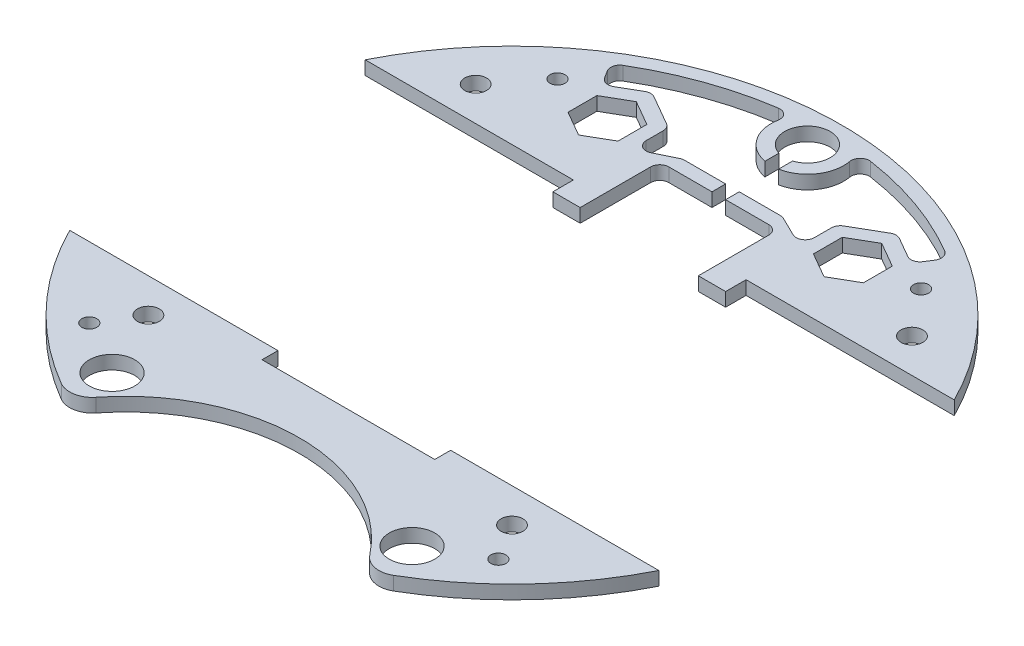
SolidWorks part; units mm, degrees
material "Acrylic (Medium-high impact)"
ref_plane "Front Plane" through (0, 0, 0) normal (0, 0, 1) x (1, 0, 0)
ref_plane "Top Plane" through (0, 0, 0) normal (0, 1, 0) x (1, 0, 0)
ref_plane "Right Plane" through (0, 0, 0) normal (1, 0, 0) x (0, 0, -1)
sketch "Sketch1" plane through (0, 0, 0) normal (0, 1, 0) x (1, 0, 0)
  line L0 (0, -85) -> (-32.4891, -64.8129) construction
  line L1 (0, -85) -> (0, 0) construction
  arc A0 (36.5434, -62.6165) -> (-36.5434, -62.6165) centre (0, 0) ccw
  arc A1 (30.0898, -61.3851) -> (-30.0898, -61.3851) centre (0, -85) ccw
  arc A2 (36.5434, -62.6165) -> (30.0898, -61.3851) centre (34.0231, -58.2982) cw
  arc A3 (-30.0898, -61.3851) -> (-36.5434, -62.6165) centre (-34.0231, -58.2982) cw
  dimension "D1" = 145
  dimension "D2" = 76.5
  dimension "D4" = 5
  dimension "D3" = 85
extrude "Boss-Extrude1" add sketch "Sketch1" along normal blind 3
sketch "solenoid placement" plane through (0, 3, 0) normal (0, 1, 0) x (1, 0, 0)
  line L4 (-19, -36) -> (19, -36)
  line L5 (-19, 28) -> (-19, -36)
  line L6 (19, 28) -> (-19, 28)
  line L7 (19, -36) -> (19, 28)
  line L8 (-19, -36) -> (19, -36)
  line L9 (-19, 28) -> (-19, -36)
  line L10 (19, 28) -> (-19, 28)
  line L11 (19, -36) -> (19, 28)
  dimension "D1" = 0
extrude "Cut-Extrude1" cut sketch "solenoid placement" against normal through all
sketch "Sketch5" plane through (0, 3, 0) normal (0, 1, 0) x (1, 0, 0)
  line L12 (-21.5, 51.1754) -> (-27, 54.3509)
  line L13 (-27, 54.3509) -> (-32.5, 51.1754)
  line L14 (-32.5, 51.1754) -> (-32.5, 44.8246)
  line L15 (-32.5, 44.8246) -> (-27, 41.6491)
  line L16 (-27, 41.6491) -> (-21.5, 44.8246)
  line L17 (-21.5, 44.8246) -> (-21.5, 51.1754)
  line L18 (-21.5, 51.1754) -> (-27, 54.3509)
  line L19 (-27, 54.3509) -> (-32.5, 51.1754)
  line L20 (-32.5, 51.1754) -> (-32.5, 44.8246)
  line L21 (-32.5, 44.8246) -> (-27, 41.6491)
  line L22 (-27, 41.6491) -> (-21.5, 44.8246)
  line L23 (-21.5, 44.8246) -> (-21.5, 51.1754)
  line L24 (21.5, 51.1754) -> (21.5, 44.8246)
  line L25 (21.5, 44.8246) -> (27, 41.6491)
  line L26 (27, 41.6491) -> (32.5, 44.8246)
  line L27 (32.5, 44.8246) -> (32.5, 51.1754)
  line L28 (32.5, 51.1754) -> (27, 54.3509)
  line L29 (27, 54.3509) -> (21.5, 51.1754)
  line L42 (21.5, 51.1754) -> (21.5, 44.8246)
  line L43 (21.5, 44.8246) -> (27, 41.6491)
  line L44 (27, 41.6491) -> (32.5, 44.8246)
  line L45 (32.5, 44.8246) -> (32.5, 51.1754)
  line L46 (32.5, 51.1754) -> (27, 54.3509)
  line L47 (27, 54.3509) -> (21.5, 51.1754)
  dimension "D1" = 0
  dimension "D2" = 0
extrude "Cut-Extrude5" cut sketch "Sketch5" against normal through all
sketch "Sketch6" plane through (0, 3, 0) normal (0, 1, 0) x (1, 0, 0)
  circle A0 centre (48, 40) radius 2.4
  circle A1 centre (40, -40) radius 2.4
  circle A2 centre (40, -40) radius 2.4 construction
  circle A3 centre (-40, -40) radius 2.4
  circle A4 centre (-40, -40) radius 2.4 construction
  circle A5 centre (48, 40) radius 2.4
  circle A6 centre (48, 40) radius 2.4 construction
  circle A7 centre (-48, 40) radius 2.4
  circle A8 centre (-48, 40) radius 2.4 construction
  circle A9 centre (-48, 40) radius 2.4
  circle A10 centre (40, -40) radius 2.4
  circle A11 centre (-40, -40) radius 2.4
  dimension "D5" = 4.8
extrude "Cut-Extrude6" cut sketch "Sketch6" against normal through all
sketch "Sketch3" plane through (0, 3, 0) normal (0, 1, 0) x (1, 0, 0)
  line L0 (-19, 28) -> (-19, 32.5)
  line L1 (72.5, -32.5) -> (-72.5, -32.5)
  line L2 (72.5, -32.5) -> (72.5, 32.5)
  line L3 (72.5, 32.5) -> (19, 32.5)
  line L4 (-72.5, -32.5) -> (-72.5, 32.5)
  line L5 (72.5, -32.5) -> (-72.5, 32.5) construction
  line L6 (72.5, 32.5) -> (-72.5, -32.5) construction
  line L7 (-19, 28) -> (19, 28)
  line L8 (19, 28) -> (19, 32.5)
  line L9 (-19, 32.5) -> (-72.5, 32.5)
  line L10 (-19, 28) -> (-19, -36) construction
  arc A0 (36.5434, -62.6165) -> (-36.5434, -62.6165) centre (0, 0) ccw construction
  point P0 (0, 0)
  dimension "D1" = 65
extrude "Cut-Extrude3" cut sketch "Sketch3" against normal through all
sketch "Sketch7" plane through (0, 3, 0) normal (0, 1, 0) x (1, 0, 0)
  line L8 (13, 28) -> (13, 43.5)
  line L9 (-13, 28) -> (13, 28)
  line L10 (-13, 43.5) -> (-13, 28)
  line L11 (11, 45.5) -> (-11, 45.5)
  line L28 (13, 28) -> (13, 43.5)
  line L29 (-13, 28) -> (13, 28)
  line L30 (-13, 43.5) -> (-13, 28)
  line L31 (11, 45.5) -> (-11, 45.5)
  arc A4 (-11, 45.5) -> (-13, 43.5) centre (-11, 43.5) ccw
  arc A5 (13, 43.5) -> (11, 45.5) centre (11, 43.5) ccw
  arc A14 (-11, 45.5) -> (-13, 43.5) centre (-11, 43.5) ccw
  arc A15 (13, 43.5) -> (11, 45.5) centre (11, 43.5) ccw
  dimension "D1" = 0
extrude "Cut-Extrude7" cut sketch "Sketch7" against normal through all
sketch "Sketch8" plane through (0, 3, 0) normal (0, 1, 0) x (1, 0, 0)
  line L0 (0, 0) -> (0, -21.9152) construction
  circle A1 centre (33, -55) radius 5
  circle A4 centre (-33, -55) radius 5
  dimension "D3" = 10
  dimension "D1" = 33
  dimension "D2" = 55
extrude "Cut-Extrude8" cut sketch "Sketch8" against normal through all
sketch "Sketch9" plane through (0, 3, 0) normal (0, 1, 0) x (1, 0, 0)
  line L0 (0, 0) -> (0, 65) construction
  line L1 (1.5, 0) -> (1.5, 60.2303)
  line L2 (-1.5, 0) -> (-1.5, 60.2303)
  line L3 (1.5, 0) -> (1.5, 65) construction
  line L4 (-1.5, 0) -> (-1.5, 65) construction
  arc A0 (1.5, 60.2303) -> (-1.5, 60.2303) centre (0, 65) ccw
  arc A1 (1.5, 0) -> (-1.5, 0) centre (0, 0) cw
  dimension "D1" = 10
  dimension "D2" = 65
  dimension "D3" = 1.5
  dimension "D4" = 1.5
extrude "Cut-Extrude9" cut sketch "Sketch9" against normal through all
sketch "Sketch10" plane through (0, 3, 0) normal (0, 1, 0) x (1, 0, 0)
  line L0 (0, 0) -> (0, -25.927) construction
  circle A0 centre (45, -48) radius 1.65
  circle A1 centre (-45, -48) radius 1.65
  circle A2 centre (40, 50) radius 1.65
  circle A3 centre (-40, 50) radius 1.65
  dimension "D3" = 3.3
  dimension "D1" = 45
  dimension "D2" = 48
  dimension "D4" = 40
  dimension "D5" = 50
extrude "Cut-Extrude10" cut sketch "Sketch10" against normal blind 10
sketch "Sketch11" plane through (0, 3, 0) normal (0, 1, 0) x (1, 0, 0)
  line L0 (-1.5, 48.5) -> (1.5, 48.5)
  line L1 (-15.6199, 46.236) -> (-11.4164, 48.2959)
  line L2 (11.4164, 48.2959) -> (15.6199, 46.236)
  line L3 (35.0267, 55.3973) -> (36.0573, 57.0273)
  line L4 (-35.0267, 55.3973) -> (-36.0573, 57.0273)
  line L11 (-18.5, 44.8246) -> (-18.5, 52.9075)
  line L12 (-18.5, 52.9075) -> (-27, 57.815)
  line L13 (-27, 57.815) -> (-34, 53.7735)
  line L14 (-18.5, 48.0319) -> (-18.5, 51.7528)
  line L15 (-19.5, 53.4848) -> (-26, 57.2376)
  line L16 (-28, 57.2376) -> (-32.3362, 54.7341)
  line L19 (-1.5, 48.5) -> (-11, 48.5)
  line L20 (-1.5, 48.5) -> (-10.5363, 48.5)
  line L22 (11, 48.5) -> (1.5, 48.5)
  line L23 (10.5363, 48.5) -> (1.5, 48.5)
  line L32 (34, 53.7735) -> (27, 57.815)
  line L33 (27, 57.815) -> (18.5, 52.9075)
  line L34 (18.5, 52.9075) -> (18.5, 44.8246)
  line L35 (32.3362, 54.7341) -> (28, 57.2376)
  line L36 (26, 57.2376) -> (19.5, 53.4848)
  line L37 (18.5, 51.7528) -> (18.5, 48.0319)
  arc A0 (-7.8724, 66.4231) -> (-10.1321, 68.7575) centre (-9.8405, 66.7788) ccw
  arc A1 (7.8724, 66.4231) -> (10.1321, 68.7575) centre (9.8405, 66.7788) cw
  arc A2 (2.4, 57.3685) -> (-2.4, 57.3685) centre (0, 65) ccw
  arc A3 (0, 57) -> (7.8724, 66.4231) centre (0, 65) ccw
  arc A4 (-7.8724, 66.4231) -> (0, 57) centre (0, 65) ccw
  arc A5 (62.1257, 31.1552) -> (-62.1257, 31.1552) centre (0, 0) ccw
  arc A6 (35.3852, 59.8175) -> (10.1321, 68.7575) centre (0, 0) ccw
  arc A7 (-10.1321, 68.7575) -> (-35.3852, 59.8175) centre (0, 0) ccw
  arc A8 (36.0573, 57.0273) -> (35.3852, 59.8175) centre (34.3669, 58.0962) ccw
  arc A9 (32.3362, 54.7341) -> (35.0267, 55.3973) centre (33.3362, 56.4661) ccw
  arc A10 (28, 57.2376) -> (26, 57.2376) centre (27, 55.5056) ccw
  arc A11 (19.5, 53.4848) -> (18.5, 51.7528) centre (20.5, 51.7528) ccw
  arc A12 (18.5, 48.0319) -> (15.6199, 46.236) centre (16.5, 48.0319) cw
  arc A13 (10.5363, 48.5) -> (11.4164, 48.2959) centre (10.5363, 46.5) cw
  arc A14 (-10.5363, 48.5) -> (-11.4164, 48.2959) centre (-10.5363, 46.5) ccw
  arc A15 (-18.5, 48.0319) -> (-15.6199, 46.236) centre (-16.5, 48.0319) ccw
  arc A16 (-18.5, 51.7528) -> (-19.5, 53.4848) centre (-20.5, 51.7528) ccw
  arc A17 (-26, 57.2376) -> (-28, 57.2376) centre (-27, 55.5056) ccw
  arc A18 (-32.3362, 54.7341) -> (-35.0267, 55.3973) centre (-33.3362, 56.4661) cw
  arc A19 (-36.0573, 57.0273) -> (-35.3852, 59.8175) centre (-34.3669, 58.0962) cw
  point P27 (-6.8312, 69.1635)
  dimension "D7" = 2
  dimension "D1" = 3
  dimension "D2" = 3
  dimension "D3" = 3
  dimension "D4" = 3
  dimension "D5" = 3
  dimension "D6" = 3
extrude "Cut-Extrude11" cut sketch "Sketch11" against normal through all
equation "\"smallPulleyTeeth\"= 30"
equation "\"largePulleyTeeth\"= 30"
equation "\"eighthThick\"= 3.0mm"
equation "\"sixteenthThick\"= 1.7mm"
equation "\"quarterThick\"=6.0mm"
equation "\"OD\"= 145mm"
equation "\"puckAngle\"= 60.5deg"
equation "\"D1@Sketch1\"=\"OD\""
equation "\"puckDiam\"= 76.5mm"
equation "\"D2@Sketch1\"=\"puckDiam\""
equation "\"D1@Boss-Extrude1\"=\"eighthThick\""
equation "\"axlePress\"= 5.9mm"
equation "\"press\"= 0.2mm"
equation "\"wheelClear\"= 0.3mm"
equation "\"10-32clear\"= 4.8mm"
equation "\"6-32clear\"= 3.3mm"
equation "\"8-32clear\"= 4.0mm"
equation "\"wheelHeight\"= 22mm"
equation "\"wheelWell\"= 65mm"
equation "\"D1@Sketch3\"=\"wheelWell\""
equation "\"puckDist\"= 85mm"
equation "\"scoopFillet\"= 5mm"
equation "\"4-40clear\"= 3.0mm"
equation "\"D3@Sketch1\"=\"puckDist\""
equation "\"D4@Sketch1\"=\"scoopFillet\""
equation "\"10-32tap\"= 4.45mm"
equation "\"D5@Sketch6\"=\"10-32clear\""
equation "\"D3@Sketch10\"=\"6-32clear\""
